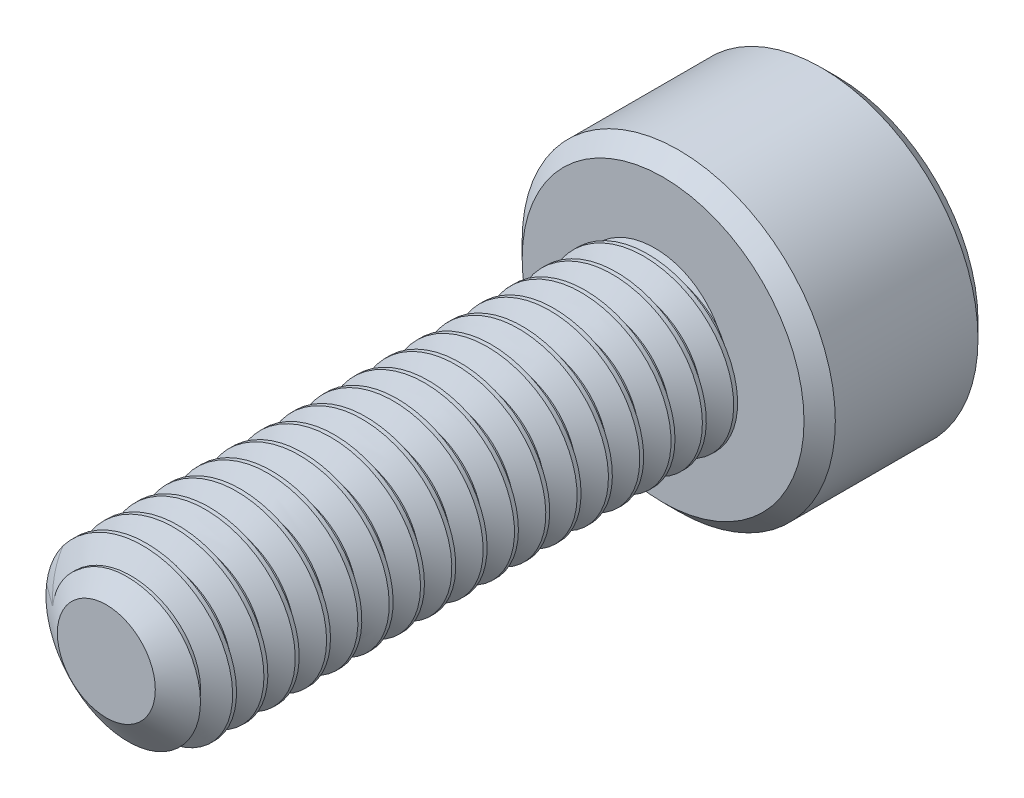
SolidWorks part; units mm, degrees
ref_plane "Front Plane" through (0, 0, 0) normal (0, 0, 1) x (1, 0, 0)
ref_plane "Top Plane" through (0, 0, 0) normal (0, 1, 0) x (1, 0, 0)
ref_plane "Right Plane" through (0, 0, 0) normal (1, 0, 0) x (0, 0, -1)
sketch "Shaft Sketch" plane through (0, 0, 0) normal (0, 0, 1) x (1, 0, 0)
  circle A0 centre (0, 0) radius 1.25
  dimension "OD" = 2.5
extrude "Shaft Extrude" add sketch "Shaft Sketch" against normal blind 8
sketch "Thread Spiral Sketch" plane through (0, 0, 0) normal (0, 0, 1) x (1, 0, 0)
  circle A0 centre (0, 0) radius 1.25 construction
  circle A1 centre (0, 0) radius 1.25
curve "Thread Helix/Spiral" pitch 0.45 height 8.45 radius 1.25 centre (0, 0, 0) axis (0, 0, -1) start towards (0, 1, 0) parameters "pitch"=0.45
sketch "Thread Cut Sketch" plane through (0, 0, 0) normal (1, 0, 0) x (0, 0, -1)
  line L0 (-0.3937, 1.25) -> (-0.225, 0.9577)
  line L1 (-0.225, 0.9577) -> (-0.1688, 0.9577)
  line L2 (-0.1688, 0.9577) -> (0, 1.25)
  line L3 (-0.3937, 1.25) -> (0, 1.25)
  line L4 (-0.1969, 1.25) -> (-0.1969, 0.9577) construction
  line L5 (-0.3094, 1.1039) -> (-0.0844, 1.1039) construction
  line L6 (0, 1.25) -> (0, -1.25) construction
  dimension "D2" = 0.225
  dimension "D3" = 60
sweep "Thread Cut Sweep" cut profiles "Thread Cut Sketch" path "Thread Helix/Spiral" align with end faces yes
sketch "End Chamfer Sketch" plane through (0, 0, 0) normal (1, 0, 0) x (0, 0, -1)
  line L0 (0.3825, 1.25) -> (0, 0.7037)
  line L1 (0, 0.7037) -> (0, 1.25)
  line L2 (0.3825, 1.25) -> (0, 1.25)
  line L3 (-0.3937, 1.25) -> (0, 1.25) construction
  line L4 (0, 0) -> (7.0209, 0) construction
  dimension "D1" = 55
  dimension "D2" = 0.254
revolve "End Chamfer Revolve" cut sketch "End Chamfer Sketch" angle 360 about L4
sketch "Head Extrude Sketch" plane through (0, 0, -8) normal (0, 0, -1) x (-1, 0, 0)
  circle A0 centre (0, 0) radius 2.25
  dimension "head dia" = 4.5
extrude "Head Extrude" add sketch "Head Extrude Sketch" along normal blind 2.5
sketch "Socket Cut Sketch" plane through (0, 0, -10.5) normal (0, 0, -1) x (-1, 0, 0)
  line L1 (0, 1.1547) -> (-1, 0.5774)
  line L2 (-1, 0.5774) -> (-1, -0.5774)
  line L3 (-1, -0.5774) -> (0, -1.1547)
  line L4 (0, -1.1547) -> (1, -0.5774)
  line L5 (1, -0.5774) -> (1, 0.5774)
  line L6 (1, 0.5774) -> (0, 1.1547)
  circle A0 centre (0, 0) radius 1 construction
  dimension "hex dia" = 2
extrude "Socket Cut Extrude" cut sketch "Socket Cut Sketch" against normal blind 1.5
sketch "Socket Entry Sketch" plane through (0, 0, -10.5) normal (0, 0, -1) x (-1, 0, 0)
  circle A0 centre (0, 0) radius 1.1547
extrude "Socket  Entry Cut Extrude" cut sketch "Socket Entry Sketch" against normal through all draft 45
chamfer "Head Chamfer" distance 0.225 angle 45 2 edges at (-2.25, 0, -10.5) (-2.25, 0, -8)
sketch "Sketch10" plane through (0, 0, -8) normal (0, 0, 1) x (1, 0, 0)
  circle A1 centre (0, 0) radius 1.25
  circle A2 centre (0, 0) radius 1.25
  dimension "D1" = 0
ref_plane "Partial Thread Plane" through (0, 0, -17) normal (0, 0, 1) x (1, 0, 0)
extrude "Partial Thread Extrude" [suppressed] add sketch "Sketch10" along normal up to surface (23 mm away) separate body up to plane "Partial Thread Plane"
chamfer "Partial Thread Chamfer" [suppressed] distance 0.05 angle 45
combine bodies "Partial Thread Combine" [suppressed] operation type add bodies to combine 107 108
equation "\"D3@Thread Helix/Spiral\"= \"screw length@Shaft Extrude\" + \"pitch@Thread Helix/Spiral\""
equation "\"D1@Thread Cut Sketch\" = \"pitch@Thread Helix/Spiral\" * .125"
equation "\"D2@Thread Cut Sketch\" = \"pitch@Thread Helix/Spiral\" * .5"
equation "\"D1@Socket Cut Extrude\" = \"hex dia@Socket Cut Sketch\" * .75"
equation "\"D1@Head Chamfer\" = \"head dia@Head Extrude Sketch\" * .05"
equation "\"D1@Partial Thread Chamfer\" = \"OD@Shaft Sketch\" * .02"
equation "\"Screw Diameter\"= 2.5mm"
equation "\"Thread Pitch\"= 0.45mm"
equation "\"Head Height\"= 2.5mm"
equation "\"Hex Size\"= 2mm"
equation "\"Head Diameter\"= 4.5mm"
equation "\"OD@Shaft Sketch\"=\"Screw Diameter\""
equation "\"pitch@Thread Helix/Spiral\"=\"Thread Pitch\""
equation "\"head dia@Head Extrude Sketch\"=\"Head Diameter\""
equation "\"head depth@Head Extrude\"=\"Head Height\""
equation "\"hex dia@Socket Cut Sketch\"=\"Hex Size\""
